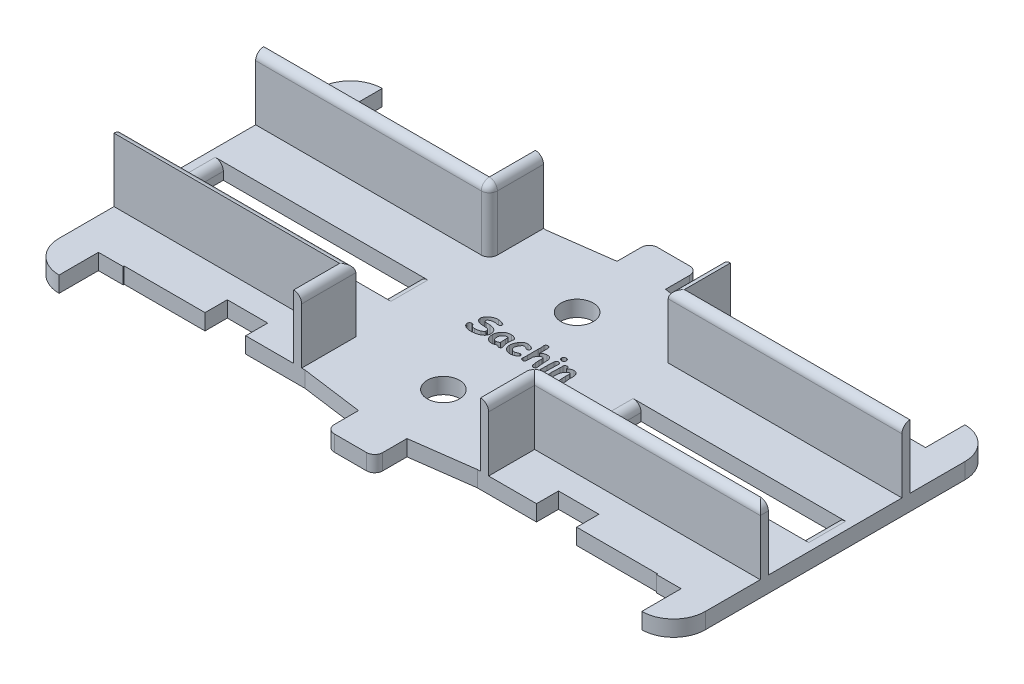
SolidWorks part; units mm, degrees
ref_plane "Front Plane" through (0, 0, 0) normal (0, 0, 1) x (1, 0, 0)
ref_plane "Top Plane" through (0, 0, 0) normal (0, 1, 0) x (1, 0, 0)
ref_plane "Right Plane" through (0, 0, 0) normal (1, 0, 0) x (0, 0, -1)
sketch "Sketch1" plane through (0, 0, 0) normal (0, 1, 0) x (1, 0, 0)
  line L1 (101.6, -50.8) -> (-101.6, -50.8)
  line L2 (101.6, -50.8) -> (101.6, 50.8)
  line L3 (101.6, 50.8) -> (-101.6, 50.8)
  line L4 (-101.6, -50.8) -> (-101.6, 50.8)
  line L5 (101.6, -50.8) -> (-101.6, 50.8) construction
  line L6 (101.6, 50.8) -> (-101.6, -50.8) construction
  point P0 (0, 0)
  dimension "D1" = 101.6
  dimension "D2" = 203.2
extrude "Boss-Extrude1" add sketch "Sketch1" along normal blind 5
sketch "Sketch2" plane through (0, 5, 0) normal (0, 1, 0) x (1, 0, 0)
  line L0 (-83.82, 50.8) -> (-83.82, 38.1)
  line L1 (101.6, 50.8) -> (-101.6, 50.8) construction
  line L2 (-83.82, 38.1) -> (-58.42, 38.1)
  line L3 (-58.42, 38.1) -> (-58.42, 31.0929)
  line L4 (-58.42, 31.0929) -> (-45.72, 31.0929)
  line L5 (-45.72, 31.0929) -> (-45.72, 38.0123)
  line L6 (-45.72, 38.0123) -> (-27.1086, 38.0123)
  line L7 (-27.1086, 38.0123) -> (-7.62, 40.64)
  line L8 (-7.62, 40.64) -> (-7.62, 50.8)
  line L9 (-7.62, 50.8) -> (-7.62, 63.5)
  line L10 (-7.62, 63.5) -> (-83.82, 63.5)
  line L11 (-83.82, 63.5) -> (-83.82, 50.8)
  line L12 (-101.6, 50.8) -> (-101.6, -50.8) construction
  dimension "D1" = 12.7
  dimension "D2" = 10.16
  dimension "D3" = 12.7
  dimension "D4" = 76.2
  dimension "D5" = 25.4
  dimension "D6" = 12.7
  dimension "D7" = 18.6114
  dimension "D8" = 17.78
extrude "Cut-Extrude1" cut sketch "Sketch2" against normal through all
mirror "Mirror2" about plane through (0, 0, 0) normal (0, 0, 1) of "Cut-Extrude1"
mirror "Mirror3" about plane through (0, 0, 0) normal (1, 0, 0) of "Mirror2" second plane through (0, 0, 0) second plane normal (0, 1, 0)
fillet "Fillet1" radius 10 4 edges at (101.6, 2.5, -50.8) (101.6, 2.5, 50.8) (-101.6, 2.5, 50.8) (-101.6, 2.5, -50.8)
sketch "Sketch5" plane through (0, 5, 0) normal (0, 1, 0) x (1, 0, 0)
  line L0 (-101.6, 23.5395) -> (-30.6562, 23.5395)
  line L1 (-101.6, 40.8) -> (-101.6, -40.8) construction
  line L2 (-30.6562, 23.5395) -> (-30.6562, 38.0123)
  line L3 (-45.72, 38.0123) -> (-27.1086, 38.0123) construction
extrude "Extrude-Thin2" add sketch "Sketch5" along normal blind 20 thin
fillet "Fillet2" radius 2.54 1 edges at (-28.1162, 15, -20.9995)
mirror "Mirror4" about plane through (0, 0, 0) normal (0, 0, 1) of "Extrude-Thin2"
mirror "Mirror5" about plane through (0, 0, 0) normal (1, 0, 0) of "Mirror4", "Extrude-Thin2"
sketch "Sketch6" plane through (0, 5, 0) normal (0, 1, 0) x (1, 0, 0)
  line L0 (-91.6, 50.8) -> (-91.6, 38.4297)
  line L1 (-91.6, 38.4297) -> (-83.82, 38.4297)
  line L2 (-83.82, 38.4297) -> (-83.82, 50.8)
  line L3 (-83.82, 50.8) -> (-91.6, 50.8) construction
  line L4 (-83.82, 50.8) -> (-83.82, 38.1) construction
  line L5 (-83.82, 50.8) -> (-91.6, 50.8)
extrude "Cut-Extrude5" cut sketch "Sketch6" against normal through all
mirror "Mirror6" about plane through (0, 0, 0) normal (0, 0, 1) of "Cut-Extrude5"
mirror "Mirror7" about plane through (0, 0, 0) normal (1, 0, 0) of "Mirror6", "Cut-Extrude5"
sketch "Sketch8" plane through (0, 5, 0) normal (0, 1, 0) x (1, 0, 0)
  circle A0 centre (0, 20.4739) radius 5.08
  circle A1 centre (0, -21.5688) radius 5.08
  dimension "D1" = 10.16
  dimension "D2" = 10.16
extrude "Cut-Extrude6" cut sketch "Sketch8" against normal through all
fillet "Fillet3" radius 2.54 4 edges at (30.6562, 25, 30.7759) (28.1162, 15, 20.9995) (66.1281, 25, 23.5395) (101.6, 25, 22.2695)
fillet "Fillet4" radius 2.54 7 edges at (-28.1162, 25, -30.7759) (-28.8601, 25, -21.7435) (28.1162, 25, -29.5059) (64.8581, 25, -20.9995) (-66.1281, 25, -20.9995) (-64.8581, 25, 20.9995) (-28.1162, 25, 29.5059)
sketch "Sketch9" plane through (0, 5, 0) normal (0, 1, 0) x (1, 0, 0)
  line L1 (-34.8166, -5.8028) -> (-96.5669, -5.8028)
  line L2 (-34.8166, -5.8028) -> (-34.8166, 5.8028)
  line L3 (-34.8166, 5.8028) -> (-96.5669, 5.8028)
  line L4 (-96.5669, -5.8028) -> (-96.5669, 5.8028)
  line L5 (-34.8166, -5.8028) -> (-96.5669, 5.8028) construction
  line L6 (-34.8166, 5.8028) -> (-96.5669, -5.8028) construction
  point P0 (-65.6918, 0)
extrude "Cut-Extrude7" cut sketch "Sketch9" against normal through all
mirror "Mirror8" about plane through (0, 0, 0) normal (1, 0, 0) of "Cut-Extrude7"
fillet "Fillet5" radius 2.54 4 edges at (96.5669, 5, 0) (34.8166, 5, 0) (-96.5669, 5, 0) (-34.8166, 5, 0)
fillet "Fillet6" radius 2.54 4 edges at (7.62, 2.5, 50.8) (7.62, 2.5, -50.8) (-7.62, 2.5, -50.8) (-7.62, 2.5, 50.8)
sketch "Sketch10" plane through (0, 5, 0) normal (0, 1, 0) x (1, 0, 0)
  text T0 "Sachin" font "Comic Sans MS" height 7.62
extrude "Cut-Extrude9" cut sketch "Sketch10" against normal through all
equation "\"0.15inin\"=0.1"
